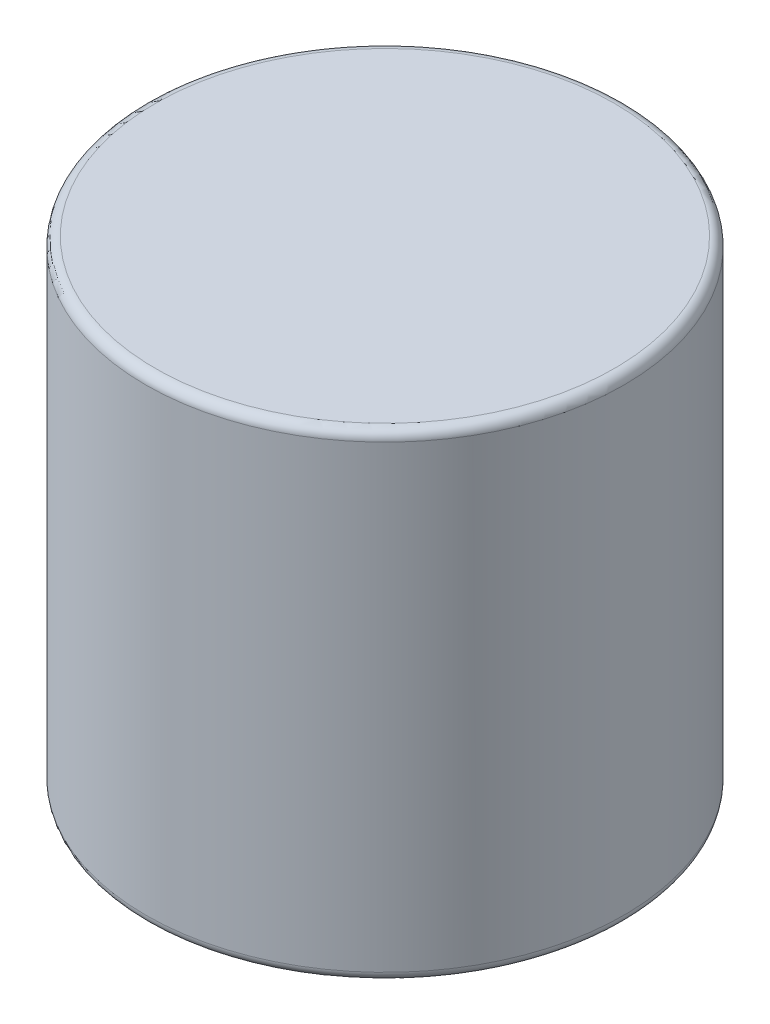
SolidWorks part; units mm, degrees
ref_plane "前视基准面" through (0, 0, 0) normal (0, 0, 1) x (1, 0, 0)
ref_plane "上视基准面" through (0, 0, 0) normal (0, 1, 0) x (1, 0, 0)
ref_plane "右视基准面" through (0, 0, 0) normal (1, 0, 0) x (0, 0, -1)
sketch "草图1" plane through (0, 0, 0) normal (0, 0, 1) x (1, 0, 0)
  line L0 (0, 2.5) -> (0, -2.5)
  line L1 (0, 2.5) -> (2.5, 2.5)
  line L3 (0, -2.5) -> (2.5, -2.5)
  line L4 (2.5, 2.5) -> (2.5, -2.5)
  line L5 (0, -2.5) -> (0, 2.5) construction
  line L6 (-1.6, 0) -> (2.5, 0) construction
  point P0 (0, 0)
  dimension "D1" = 5
  dimension "D2" = 2.5
revolve "旋转2" add sketch "草图1" angle 360 about L0
fillet "圆角1" radius 0.1 2 edges at (0, -2.5, 2.5) (0, 2.5, 2.5)
ref_axis "基准轴1" through (1.65, 0, 0) along (-1, 0, 0)
ref_plane "基准面1" through (0, 0, 0) normal (0, 0.7071, 0.7071) x (-1, 0, 0)
ref_plane "基准面2" through (0, 0, 0) normal (0, 0.7071, -0.7071) x (-1, 0, 0)
